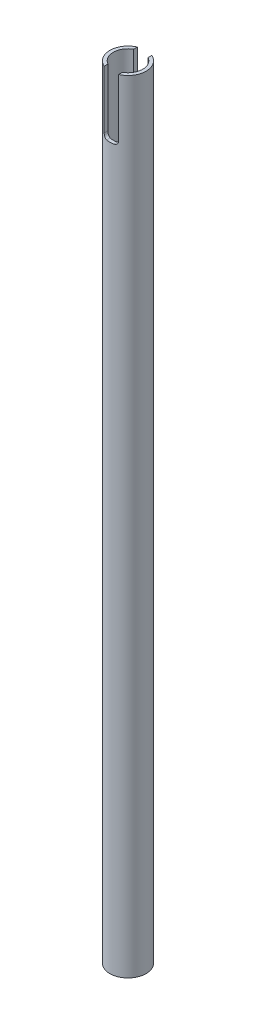
SolidWorks part; units mm, degrees
material "AISI 4130 Steel, normalized at 870C"
ref_plane "X-Y Datum" through (0, 0, 0) normal (0, 0, 1) x (1, 0, 0)
ref_plane "X-Z Datum" through (0, 0, 0) normal (0, 1, 0) x (1, 0, 0)
ref_plane "Y-Z Datum" through (0, 0, 0) normal (1, 0, 0) x (0, 0, -1)
sketch "Sketch1" plane through (0, 0, 0) normal (0, 1, 0) x (1, 0, 0)
  circle A0 centre (0, 0) radius 6.4643
  circle A1 centre (0, 0) radius 7.9375
  dimension "D1" = 1.4732
  dimension "D2" = 15.875
extrude "Boss-Extrude1" add sketch "Sketch1" along normal offset from surface (343.0551 mm away) 25.4 from surface at -164.6707
sketch "Sketch2" plane through (0, 0, 0) normal (0, 0, 1) x (1, 0, 0)
  line L0 (0, 178.3845) -> (0, 151.397) construction
  line L1 (-3.175, 178.3845) -> (3.175, 178.3845)
  line L2 (-3.175, 178.3845) -> (-3.175, 152.9845)
  line L3 (-1.5875, 151.397) -> (1.5875, 151.397)
  line L4 (3.175, 178.3845) -> (3.175, 152.9845)
  line L5 (-3.175, 186.6395) -> (-3.175, 154.572) construction
  line L8 (0, -202.3738) -> (0, 202.3738) construction
  arc A0 (-3.175, 152.9845) -> (-1.5875, 151.397) centre (-1.5875, 152.9845) ccw
  arc A1 (3.175, 152.9845) -> (1.5875, 151.397) centre (1.5875, 152.9845) cw
  dimension "D1" = 1.5875
extrude "Cut-Extrude1" cut sketch "Sketch2" against normal through all both and the other way through all
